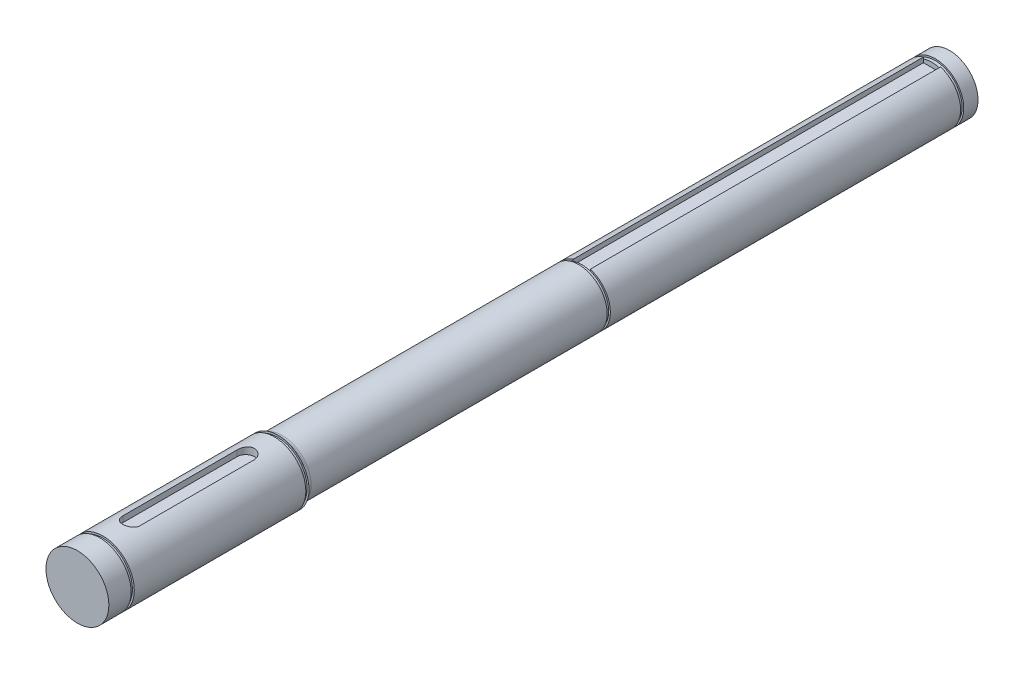
SolidWorks part; units mm, degrees
ref_plane "Front Plane" through (0, 0, 0) normal (0, 0, 1) x (1, 0, 0)
ref_plane "Top Plane" through (0, 0, 0) normal (0, 1, 0) x (1, 0, 0)
ref_plane "Right Plane" through (0, 0, 0) normal (1, 0, 0) x (0, 0, -1)
sketch "Sketch2" plane through (0, 0, 0) normal (0, 0, 1) x (1, 0, 0)
  circle A0 centre (0, 0) radius 10
extrude "Boss-Extrude1" add sketch "Sketch2" along normal blind 235
ref_plane "Plane1" through (0, 0, 5) normal (0, 0, -1) x (-1, 0, 0)
sketch "Sketch3" plane through (0, 0, 5) normal (0, 0, -1) x (-1, 0, 0)
  circle A0 centre (0, 0) radius 10
  circle A1 centre (0, 0) radius 9.43
  dimension "D1" = 18.86
extrude "Cut-Extrude2" cut sketch "Sketch3" against normal blind 1.1
ref_plane "Plane2" through (0, 0, 67.35) normal (0, 0, -1) x (-1, 0, 0)
mirror "Mirror1" about plane through (0, 0, 67.35) normal (0, 0, -1) of "Cut-Extrude2"
sketch "Sketch4" plane through (0, 0, 67.35) normal (0, 0, -1) x (-1, 0, 0)
  line L0 (0, -10) -> (0, 7.81) construction
  line L1 (-3, 7.81) -> (3, 7.81)
  line L2 (-3, 7.81) -> (-3, 10.8778)
  line L3 (-3, 10.8778) -> (3, 10.8778)
  line L4 (3, 10.8778) -> (3, 7.81)
  circle A0 centre (0, 0) radius 10 construction
  point P9 (0, 7.81)
  dimension "D1" = 17.81
  dimension "D2" = 6
extrude "Cut-Extrude3" cut sketch "Sketch4" against normal mid plane 122.5
ref_plane "Plane3" through (0, 0, 235) normal (0, 0, 1) x (1, 0, 0)
sketch "Sketch5" plane through (0, 0, 235) normal (0, 0, 1) x (1, 0, 0)
  circle A0 centre (0, 0) radius 11
extrude "Boss-Extrude2" add sketch "Sketch5" along normal blind 70
fillet "Fillet3" radius 2 1 edges at (10, 0, 235)
sketch "Sketch6" plane through (0, 0, 235) normal (0, 0, 1) x (1, 0, 0)
  circle A0 centre (0, 0) radius 11
  circle A1 centre (0, 0) radius 10.35
extrude "Cut-Extrude4" cut sketch "Sketch6" along normal blind 1.1
ref_plane "Plane4" through (0, 0, 266.1) normal (0, 0, 1) x (1, 0, 0)
mirror "Mirror2" about plane through (0, 0, 266.1) normal (0, 0, 1) of "Cut-Extrude4"
ref_plane "Plane5" through (0, 11, 0) normal (0, 1, 0) x (1, 0, 0)
sketch "Sketch8" plane through (0, 11, 0) normal (0, 1, 0) x (1, 0, 0)
  line L0 (0, -236.1) -> (0, -246.1) construction
  line L1 (11, -236.1) -> (-11, -236.1) construction
  line L2 (0, -246.1) -> (0, -286.1) construction
  line L3 (3, -246.1) -> (3, -286.1)
  line L4 (-3, -246.1) -> (-3, -286.1)
  arc A0 (3, -246.1) -> (-3, -246.1) centre (0, -246.1) ccw
  arc A1 (-3, -286.1) -> (3, -286.1) centre (0, -286.1) ccw
  point P5 (0, -266.1)
  dimension "D1" = 10
  dimension "D2" = 40
  dimension "D3" = 6
extrude "Cut-Extrude5" cut sketch "Sketch8" against normal blind 2.5
